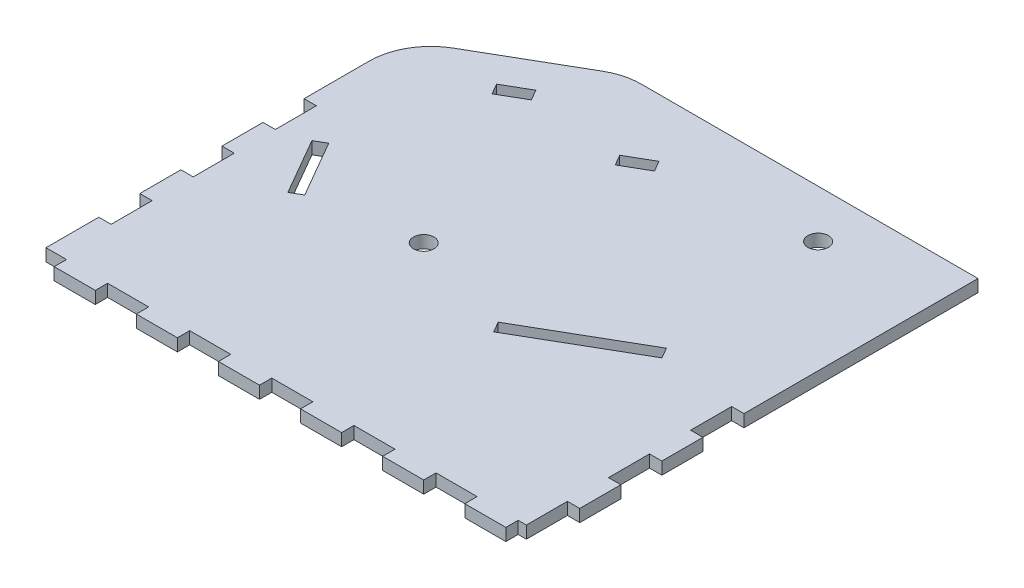
SolidWorks part; units mm, degrees
ref_plane "Alzado" through (0, 0, 0) normal (0, 0, 1) x (1, 0, 0)
ref_plane "Planta" through (0, 0, 0) normal (0, 1, 0) x (1, 0, 0)
ref_plane "Vista lateral" through (0, 0, 0) normal (1, 0, 0) x (0, 0, -1)
sketch "Croquis1" plane through (0, 0, 0) normal (0, 1, 0) x (1, 0, 0)
  line L0 (0, 0) -> (120, 0) construction
  line L1 (0, 0) -> (45, 0)
  line L2 (45, 0) -> (45, 50) construction
  line L3 (45, 0) -> (92.72, 0)
  line L4 (92.72, 0) -> (92.72, 98.34) construction
  line L5 (0, 0) -> (0, 81.7078) construction
  line L6 (38.0227, 110) -> (120, 110)
  line L7 (120, 110) -> (120, 0) construction
  line L8 (0, 0) -> (0, 62.3) construction
  line L9 (0, 62.3) -> (7.3, 62.3) construction
  line L10 (7.3, 62.3) -> (20.3, 39.7833) construction
  line L11 (7.3, 62.3) -> (9.8981, 63.8) construction
  line L12 (20.3, 39.7833) -> (22.8981, 41.2833) construction
  line L13 (22.8981, 41.2833) -> (9.8981, 63.8) construction
  line L14 (16.3981, 52.5417) -> (12.3981, 59.4699)
  line L15 (12.3981, 59.4699) -> (9.8, 57.9699)
  line L16 (12.3981, 59.4699) -> (20.3981, 45.6135)
  line L17 (20.3981, 45.6135) -> (17.8, 44.1135)
  line L18 (9.8, 57.9699) -> (17.8, 44.1135)
  line L19 (0, 0) -> (56.92, 0)
  line L20 (56.92, 0) -> (56.92, 34.36) construction
  line L21 (56.92, 34.36) -> (110.6136, 65.36) construction
  line L22 (56.92, 34.36) -> (58.42, 31.7619) construction
  line L23 (58.42, 31.7619) -> (112.1136, 62.7619) construction
  line L24 (112.1136, 62.7619) -> (110.6136, 65.36) construction
  line L25 (83.7668, 49.86) -> (70.7764, 42.36)
  line L26 (70.7764, 42.36) -> (72.2764, 39.7619)
  line L27 (72.2764, 39.7619) -> (85.2668, 47.2619)
  line L28 (85.2668, 47.2619) -> (83.7668, 49.86) construction
  line L29 (96.7572, 57.36) -> (98.2572, 54.7619)
  line L30 (83.7668, 49.86) -> (96.7572, 57.36)
  line L31 (85.2668, 47.2619) -> (98.2572, 54.7619)
  line L32 (0, 110) -> (18.41, 110)
  line L33 (18.41, 110) -> (18.41, 87.77) construction
  line L34 (18.41, 87.77) -> (31.4004, 95.27) construction
  line L35 (31.4004, 95.27) -> (29.9004, 97.8681) construction
  line L36 (18.41, 87.77) -> (16.91, 90.3681) construction
  line L37 (29.9004, 97.8681) -> (16.91, 90.3681) construction
  line L38 (24.9052, 91.52) -> (23.4052, 94.1181) construction
  line L39 (23.4052, 94.1181) -> (26.4363, 95.8681)
  line L40 (26.4363, 95.8681) -> (27.9363, 93.27)
  line L41 (27.9363, 93.27) -> (24.9052, 91.52)
  line L42 (20.3741, 92.3681) -> (21.8741, 89.77)
  line L43 (23.4052, 94.1181) -> (20.3741, 92.3681)
  line L44 (24.9052, 91.52) -> (21.8741, 89.77)
  line L45 (23.4052, 94.1181) -> (20.3741, 92.3681)
  line L46 (24.9052, 91.52) -> (21.8741, 89.77)
  line L47 (0, 110) -> (48.41, 110) construction
  line L48 (48.41, 110) -> (48.41, 87.77) construction
  line L49 (56.4363, 95.8681) -> (57.9363, 93.27)
  line L50 (48.41, 87.77) -> (61.4004, 95.27) construction
  line L51 (54.9052, 91.52) -> (51.8741, 89.77)
  line L52 (53.4052, 94.1181) -> (50.3741, 92.3681)
  line L53 (61.4004, 95.27) -> (59.9004, 97.8681) construction
  line L54 (57.9363, 93.27) -> (54.9052, 91.52)
  line L55 (48.41, 87.77) -> (46.91, 90.3681) construction
  line L56 (54.9052, 91.52) -> (51.8741, 89.77)
  line L57 (50.3741, 92.3681) -> (51.8741, 89.77)
  line L58 (59.9004, 97.8681) -> (46.91, 90.3681) construction
  line L59 (53.4052, 94.1181) -> (56.4363, 95.8681)
  line L60 (48.41, 110) -> (48.41, 87.77) construction
  line L61 (53.4052, 94.1181) -> (50.3741, 92.3681)
  line L62 (54.9052, 91.52) -> (53.4052, 94.1181) construction
  line L63 (60, 0) -> (60, 3)
  line L64 (65, 3) -> (55, 3)
  line L65 (55, 3) -> (55, 0)
  line L66 (55, 0) -> (45, 0)
  line L67 (45, 0) -> (45, 3)
  line L68 (45, 3) -> (35, 3)
  line L69 (35, 3) -> (35, 0)
  line L70 (35, 0) -> (25, 0)
  line L71 (25, 0) -> (25, 3)
  line L72 (25, 3) -> (15, 3)
  line L73 (15, 3) -> (15, 0)
  line L74 (15, 0) -> (5, 0)
  line L75 (5, 0) -> (5, 3)
  line L76 (5, 3) -> (0, 3)
  line L77 (115, 3) -> (120, 3) construction
  line L78 (115, 0) -> (115, 3)
  line L79 (105, 3) -> (105, 0)
  line L80 (95, 3) -> (105, 3)
  line L81 (95, 0) -> (95, 3)
  line L82 (85, 3) -> (85, 0)
  line L83 (75, 3) -> (85, 3)
  line L84 (75, 0) -> (75, 3)
  line L85 (65, 3) -> (65, 0)
  line L86 (5, 0) -> (15, 0)
  line L87 (25, 0) -> (35, 0)
  line L88 (45, 0) -> (55, 0)
  line L89 (65, 0) -> (75, 0)
  line L90 (85, 0) -> (95, 0)
  line L91 (105, 0) -> (115, 0)
  line L92 (7.5, 94.6982) -> (30.5227, 107.9904)
  line L93 (0, 40.8539) -> (3, 40.8539)
  line L94 (3, 45.8539) -> (3, 35.8539)
  line L95 (3, 35.8539) -> (0, 35.8539)
  line L96 (0, 35.8539) -> (0, 25.8539)
  line L97 (0, 25.8539) -> (3, 25.8539)
  line L98 (3, 25.8539) -> (3, 15.8539)
  line L99 (3, 15.8539) -> (0, 15.8539)
  line L100 (3, 65.8539) -> (0, 65.8539)
  line L101 (3, 55.8539) -> (3, 65.8539)
  line L102 (0, 55.8539) -> (3, 55.8539)
  line L103 (3, 45.8539) -> (0, 45.8539)
  line L104 (0, 81.7078) -> (0, 65.8539)
  line L105 (0, 55.8539) -> (0, 45.8539)
  line L106 (0, 35.8539) -> (0, 25.8539)
  line L107 (0, 15.8539) -> (0, 3)
  line L108 (120, 3) -> (120, 53) construction
  line L109 (120, 3) -> (120, 28) construction
  line L110 (120, 28) -> (117, 28) construction
  line L111 (117, 33) -> (117, 23)
  line L112 (117, 23) -> (120, 23)
  line L113 (120, 23) -> (120, 13) construction
  line L114 (120, 13) -> (117, 13)
  line L115 (117, 13) -> (117, 3)
  line L116 (117, 43) -> (117, 53)
  line L117 (120, 43) -> (117, 43)
  line L118 (117, 33) -> (120, 33)
  line L119 (117, 53) -> (120, 53)
  line L120 (115, 3) -> (117, 3)
  line L121 (120, 110) -> (120, 53)
  line L122 (120, 43) -> (120, 33)
  line L123 (120, 23) -> (120, 13)
  circle A0 centre (45, 50) radius 2.5
  circle A1 centre (92.72, 98.34) radius 2.5
  arc A2 (7.5, 94.6982) -> (0, 81.7078) centre (15, 81.7078) ccw
  arc A3 (38.0227, 110) -> (30.5227, 107.9904) centre (38.0227, 95) ccw
  dimension "D3" = 5
  dimension "D6" = 5
  dimension "D7" = 15
  dimension "D24" = 15
  dimension "D1" = 120
  dimension "D2" = 45
  dimension "D4" = 47.72
  dimension "D5" = 98.34
  dimension "D8" = 62.3
  dimension "D9" = 7.3
  dimension "D10" = 120
  dimension "D11" = 26
  dimension "D12" = 90
  dimension "D13" = 3
  dimension "D14" = 3
  dimension "D15" = 90
  dimension "D16" = 8
  dimension "D17" = 56.92
  dimension "D18" = 34.36
  dimension "D19" = 120
  dimension "D20" = 90
  dimension "D21" = 3
  dimension "D22" = 62
  dimension "D23" = 15
  dimension "D25" = 22.23
  dimension "D26" = 60
  dimension "D27" = 15
  dimension "D28" = 90
  dimension "D29" = 90
  dimension "D30" = 3
  dimension "D31" = 3
  dimension "D32" = 3.5
  dimension "D33" = 50
  dimension "D34" = 22.23
  dimension "D35" = 60
  dimension "D36" = 15
  dimension "D37" = 90
  dimension "D38" = 90
  dimension "D39" = 3
  dimension "D40" = 3
  dimension "D41" = 3.5
  dimension "D42" = 3
  dimension "D43" = 5
  dimension "D44" = 10
  dimension "D45" = 10
  dimension "D46" = 10
  dimension "D47" = 10
  dimension "D48" = 10
  dimension "D49" = 120
  dimension "D50" = 3
  dimension "D51" = 5
  dimension "D52" = 10
  dimension "D53" = 10
  dimension "D54" = 50
  dimension "D55" = 25
  dimension "D56" = 3
  dimension "D57" = 5
  dimension "D58" = 10
extrude "Saliente-Extruir1" add sketch "Croquis1" along normal blind 3 contours L7 L6 L5 L0 L3 A1 A0 L31 L27 L26 L25 L30 L29 L18 L15 L14 L16 L17 L41 L44 L42 L43 L39 L40 L52 L59 L49 L54 L51 L57 region at (61.4228, 0, -54.5975)
